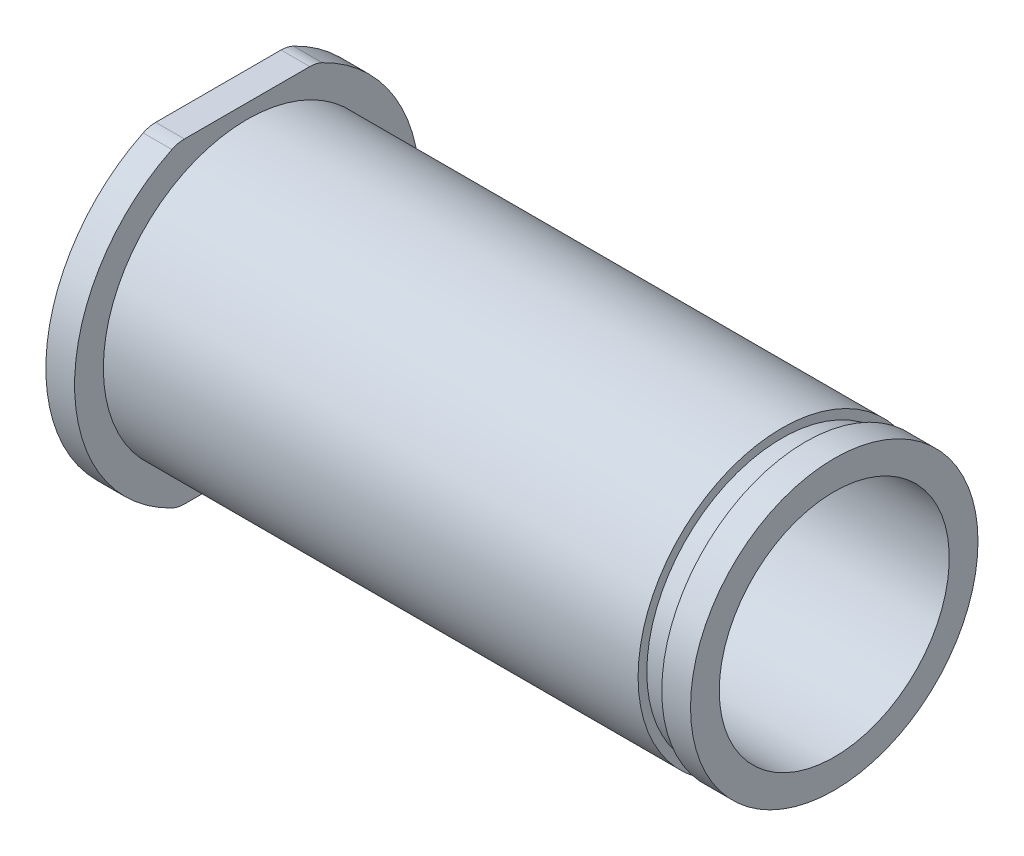
SolidWorks part; units mm, degrees
material "6061 Alloy"
ref_plane "Front Plane" through (0, 0, 0) normal (0, 0, 1) x (1, 0, 0)
ref_plane "Top Plane" through (0, 0, 0) normal (0, 1, 0) x (1, 0, 0)
ref_plane "Right Plane" through (0, 0, 0) normal (1, 0, 0) x (0, 0, -1)
sketch "Sketch1" plane through (0, 0, 0) normal (0, 0, 1) x (1, 0, 0)
  line L0 (0, 0) -> (68.0212, 0) construction
  line L1 (0, 19.05) -> (0, 12.7)
  line L2 (0, 12.7) -> (68.0212, 12.7)
  line L3 (68.0212, 12.7) -> (68.0212, 15.875)
  line L4 (68.0212, 15.875) -> (64.8462, 15.875)
  line L5 (64.8462, 15.875) -> (64.8462, 14.9098)
  line L6 (64.8462, 14.9098) -> (62.23, 14.9098)
  line L7 (62.23, 14.9098) -> (62.23, 15.875)
  line L8 (62.23, 15.875) -> (3.175, 15.875)
  line L9 (3.175, 15.875) -> (3.175, 19.05)
  line L10 (3.175, 19.05) -> (0, 19.05)
  dimension "D1" = 3.175
  dimension "D2" = 3.175
  dimension "D3" = 31.75
  dimension "D4" = 29.8196
  dimension "D5" = 2.6162
  dimension "D6" = 38.1
  dimension "D7" = 25.4
  dimension "D8" = 62.23
revolve "Revolve1" add sketch "Sketch1" angle 360 about L0
sketch "Sketch2" plane through (0, 0, 0) normal (-1, 0, 0) x (0, 0, 1)
  line L0 (0, 17.4625) -> (0, -17.4625) construction
  line L1 (-7.6134, 17.4625) -> (7.6134, 17.4625)
  line L2 (-7.6134, 17.4625) -> (-7.6134, 19.05)
  line L3 (-7.6134, 19.05) -> (7.6134, 19.05)
  line L4 (7.6134, 17.4625) -> (7.6134, 19.05)
  line L6 (-7.6134, -17.4625) -> (7.6134, -17.4625)
  line L7 (-7.6134, -17.4625) -> (-7.6134, -19.05)
  line L8 (-7.6134, -19.05) -> (7.6134, -19.05)
  line L9 (7.6134, -17.4625) -> (7.6134, -19.05)
  circle A0 centre (0, 0) radius 19.05 construction
  dimension "D1" = 38.1
  dimension "D2" = 34.925
extrude "Cut-Extrude1" cut sketch "Sketch2" against normal through all
fillet "Fillet1" radius 3.175 4 edges at (1.5875, -17.4625, -7.6134) (1.5875, -17.4625, 7.6134) (1.5875, 17.4625, 7.6134) (1.5875, 17.4625, -7.6134)
